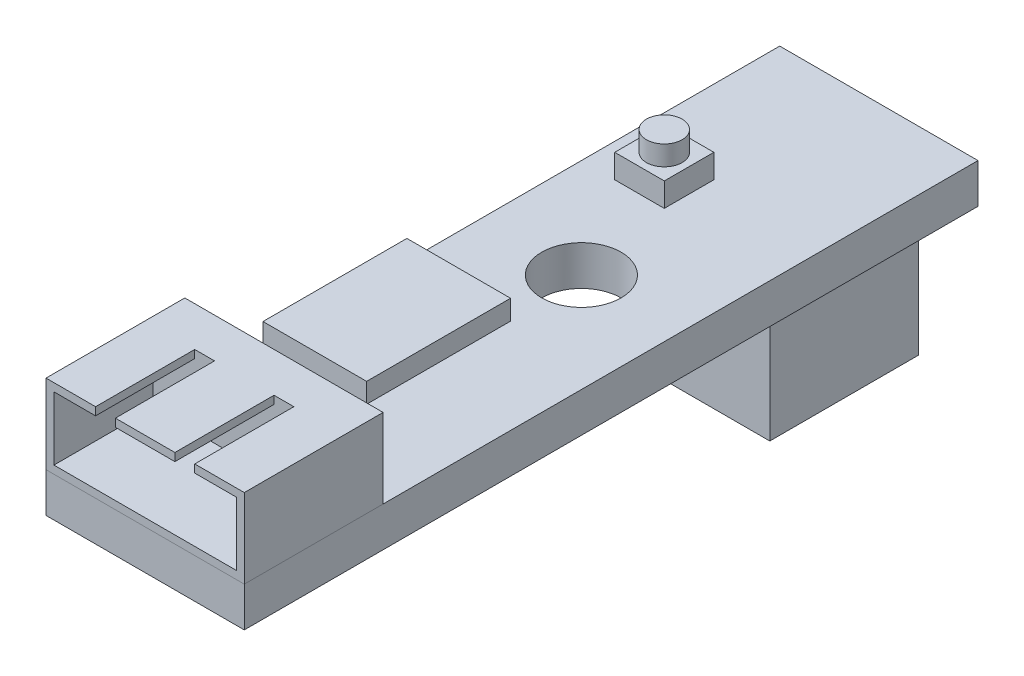
SolidWorks part; units mm, degrees
ref_plane "前视基准面" through (0, 0, 0) normal (0, 0, 1) x (1, 0, 0)
ref_plane "上视基准面" through (0, 0, 0) normal (0, 1, 0) x (1, 0, 0)
ref_plane "右视基准面" through (0, 0, 0) normal (1, 0, 0) x (0, 0, -1)
sketch "草图1" plane through (0, 0, 0) normal (0, 1, 0) x (1, 0, 0)
  line L1 (-5, 18.5) -> (5, 18.5)
  line L2 (-5, 18.5) -> (-5, -18.5)
  line L3 (-5, -18.5) -> (5, -18.5)
  line L4 (5, 18.5) -> (5, -18.5)
  line L5 (-5, 18.5) -> (5, -18.5) construction
  line L6 (-5, -18.5) -> (5, 18.5) construction
  point P0 (0, 0)
  dimension "D1" = 37
  dimension "D2" = 10
extrude "凸台-拉伸1" add sketch "草图1" along normal blind 2
sketch "草图2" plane through (0, 2, 0) normal (0, 1, 0) x (1, 0, 0)
  line L0 (-5, 18.5) -> (-5, -18.5) construction
  line L1 (-5, -11.5) -> (5, -11.5)
  line L2 (-5, -11.5) -> (-5, -18.5)
  line L3 (-5, -18.5) -> (5, -18.5)
  line L4 (5, -11.5) -> (5, -18.5)
  dimension "D1" = 7
extrude "凸台-拉伸2" add sketch "草图2" along normal blind 4 separate body
sketch "草图3" plane through (0, 0, 18.5) normal (0, 0, 1) x (1, 0, 0)
  line L4 (-5, 2) -> (5, 2)
  line L5 (5, 2) -> (5, 6)
  line L6 (5, 6) -> (-5, 6)
  line L7 (-5, 6) -> (-5, 2)
  line L8 (-5, 2) -> (5, 2) construction
  line L9 (5, 2) -> (5, 6) construction
  line L10 (5, 6) -> (-5, 6) construction
  line L11 (-5, 6) -> (-5, 2) construction
  line L12 (0, 5.6) -> (0, 7.429) construction
  line L13 (1.5, 6) -> (1.5, 5.6)
  line L14 (-2.5, 6) -> (-1.5, 6)
  line L15 (-2.5, 6) -> (-2.5, 5.6)
  line L16 (-4.6, 2.4) -> (4.6, 2.4)
  line L17 (4.6, 2.4) -> (4.6, 5.6)
  line L18 (4.6, 5.6) -> (-4.6, 5.6)
  line L19 (-4.6, 5.6) -> (-4.6, 2.4)
  line L20 (-4.6, 2.4) -> (4.6, 2.4)
  line L21 (4.6, 2.4) -> (4.6, 5.6)
  line L22 (4.6, 5.6) -> (2.5, 5.6)
  line L23 (-4.6, 5.6) -> (-4.6, 2.4)
  line L24 (-2.5, 5.6) -> (-1.5, 5.6) construction
  line L25 (-1.5, 6) -> (-1.5, 5.6)
  line L26 (2.5, 6) -> (2.5, 5.6)
  line L27 (2.5, 6) -> (1.5, 6)
  line L28 (-1.5, 5.6) -> (-2.5, 5.6) construction
  line L29 (-2.5, 5.6) -> (-4.6, 5.6)
  line L30 (2.5, 5.6) -> (1.5, 5.6) construction
  line L31 (1.5, 5.6) -> (-1.5, 5.6)
  dimension "D3" = 3
  dimension "D4" = 1
  dimension "D1" = 0
  dimension "D2" = 0.4
extrude "切除-拉伸1" cut sketch "草图3" against normal blind 5
sketch "草图4" plane through (0, 0, 0) normal (0, -1, 0) x (1, 0, 0)
  line L0 (0, 18.5) -> (0, -18.5) construction
  line L1 (-5, 18.5) -> (5, 18.5) construction
  line L2 (5, -18.5) -> (-5, -18.5) construction
  line L3 (5, -18.5) -> (-5, -18.5) construction
  circle A0 centre (0, -3.5) radius 2
  dimension "D1" = 4
  dimension "D2" = 15
extrude "切除-拉伸2" cut sketch "草图4" against normal blind 5
sketch "草图5" plane through (0, 0, 0) normal (0, -1, 0) x (1, 0, 0)
  line L0 (5, 18.5) -> (5, -18.5) construction
  line L1 (-2, -10) -> (3, -10)
  line L2 (-3, -11) -> (-3, -17.5)
  line L3 (-3, -17.5) -> (3, -17.5)
  line L4 (3, -10) -> (3, -17.5)
  line L5 (5, -18.5) -> (-5, -18.5) construction
  line L6 (-3, -11) -> (-2, -10)
  point P0 (-3, -10)
  dimension "D1" = 6
  dimension "D2" = 7.5
  dimension "D3" = 2
  dimension "D4" = 1
extrude "凸台-拉伸3" add sketch "草图5" along normal blind 7
sketch "草图6" plane through (0, 2, 0) normal (0, 1, 0) x (1, 0, 0)
  line L0 (-5, 18.5) -> (-5, -18.5) construction
  line L1 (-5, -0.3) -> (0.2273, -0.3)
  line L2 (-5, -0.3) -> (-5, -7.5587)
  line L3 (-5, -7.5587) -> (0.2273, -7.5587)
  line L4 (0.2273, -0.3) -> (0.2273, -7.5587)
extrude "凸台-拉伸4" add sketch "草图6" along normal blind 1
sketch "草图7" plane through (0, 2, 0) normal (0, 1, 0) x (1, 0, 0)
  line L0 (5, 18.5) -> (-5, 18.5) construction
  line L1 (-3.3201, 11) -> (-0.8201, 11)
  line L2 (-3.3201, 11) -> (-3.3201, 8.5)
  line L3 (-3.3201, 8.5) -> (-0.8201, 8.5)
  line L4 (-0.8201, 11) -> (-0.8201, 8.5)
  dimension "D1" = 2.5
  dimension "D2" = 10
extrude "凸台-拉伸5" add sketch "草图7" along normal blind 1.2 separate body
sketch "草图8" plane through (0, 3.2, 0) normal (0, 1, 0) x (1, 0, 0)
  line L0 (-3.3201, 11) -> (-0.8201, 8.5) construction
  line L1 (-2.0701, 9.75) -> (-0.8201, 11) construction
  line L2 (-0.8201, 11) -> (-3.3201, 11) construction
  line L3 (-0.8201, 8.5) -> (-0.8201, 11) construction
  line L4 (-3.3201, 11) -> (-3.3201, 8.5) construction
  circle A0 centre (-2.0701, 9.75) radius 0.9
  dimension "D1" = 1.8
extrude "凸台-拉伸6" add sketch "草图8" along normal blind 1
sketch "草图9" plane through (0, -7, 0) normal (0, -1, 0) x (1, 0, 0)
  line L0 (0, -12) -> (0, -15.6) construction
  line L1 (3, -10) -> (-2, -10) construction
  circle A0 centre (0, -12) radius 1.5
  circle A1 centre (0, -15.6) radius 1.5
  dimension "D1" = 3
  dimension "D3" = 2
  dimension "D2" = 3.6
extrude "切除-拉伸3" cut sketch "草图9" against normal blind 1
ref_axis "基准轴1" through (0, -6, -12) along (0, -1, 0)
ref_plane "基准面1" through (0, 0, 0) normal (1, 0, 0) x (0, -1, 0)
sketch "草图10" plane through (0, 0, 0) normal (1, 0, 0) x (0, -1, 0)
  line L0 (6, 10.5) -> (6, 13.5) construction
  line L1 (6, 10.5) -> (6, 13.5) construction
  line L3 (6, 12) -> (6.6918, 12)
  line L5 (6, 12) -> (6, 10.5)
  spline S0 degree 2 poles (6, 10.5) (6.763, 11.0996) (6.6918, 12) knots 0 0 0 1 1 1
revolve "旋转1" add sketch "草图10" angle 360 about L3
sketch "草图11" plane through (0, 0, 0) normal (1, 0, 0) x (0, -1, 0)
  line L0 (6, 14.1) -> (6, 17.1) construction
  line L1 (6, 14.1) -> (6, 15.6)
  line L2 (6, 15.6) -> (6.6997, 15.6)
  line L3 (6, 15.6) -> (6, 17.1) construction
  spline S0 degree 2 poles (6, 14.1) (6.7246, 14.6772) (6.6997, 15.6) knots 0 0 0 1 1 1
  dimension "D1" = 0.6997
revolve "旋转2" add sketch "草图11" angle 360 about L2
sketch "草图12" plane through (0, 2, 0) normal (0, 1, 0) x (1, 0, 0)
  circle A0 centre (0, 3.5) radius 3.2
  circle A1 centre (0, 3.5) radius 2 construction
  dimension "D1" = 1.2
